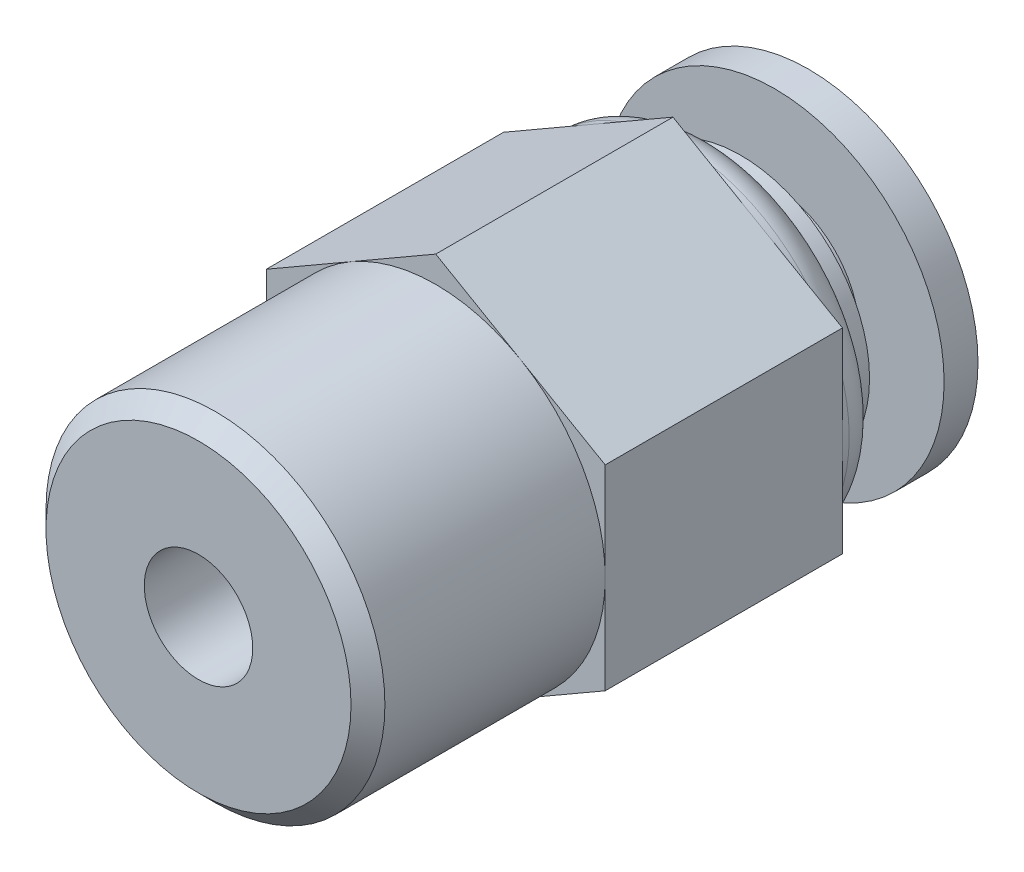
SolidWorks part; units mm, degrees
note: The reader was unsure of these and kept them because the rebuilt part matched: shared geometry of "Эскиз1<4>", "Эскиз1<5>", "Эскиз1<6>", "Эскиз1<8>", "Эскиз1<10>", "Эскиз1<11>".
material "Простая углеродистая сталь"
ref_plane "Спереди" through (0, 0, 0) normal (0, 0, 1) x (1, 0, 0)
ref_plane "Сверху" through (0, 0, 0) normal (0, 1, 0) x (1, 0, 0)
ref_plane "Справа" through (0, 0, 0) normal (1, 0, 0) x (0, 0, -1)
sketch "Эскиз1" plane through (0, 0, 0) normal (0, 0, 1) x (1, 0, 0)
  line L3 (0, 5.7735) -> (-5, 2.8868)
  line L4 (-5, 2.8868) -> (-5, -2.8868)
  line L5 (-5, -2.8868) -> (0, -5.7735)
  line L6 (0, -5.7735) -> (5, -2.8868)
  line L7 (5, -2.8868) -> (5, 2.8868)
  line L8 (5, 2.8868) -> (0, 5.7735)
  circle A0 centre (0, 0) radius 1.6
  circle A1 centre (0, 0) radius 3
  circle A2 centre (0, 0) radius 5 construction
  circle A3 centre (0, 0) radius 5
  circle A4 centre (0, 0) radius 4.3
  circle A5 centre (0, 0) radius 5
  circle A6 centre (0, 0) radius 3.8
  dimension "D1" = 3.2
  dimension "D2" = 6
  dimension "D3" = 10
  dimension "D4" = 8.6
  dimension "D5" = 10
  dimension "D6" = 10
extrude "Бобышка-Вытянуть2" add sketch "Эскиз1" along normal blind 7 contours L3 L4 L5 L6 L7 L8
extrude "Бобышка-Вытянуть3" add sketch "Эскиз1<4>" against normal blind 1.2 contours A3
sketch "Эскиз1<4>" plane through (0, 0, 0) normal (0, 0, 1) x (1, 0, 0) same geometry as "Эскиз1"
extrude "Бобышка-Вытянуть4" add sketch "Эскиз1<5>" along normal blind 14 contours A5
sketch "Эскиз1<5>" plane through (0, 0, 0) normal (0, 0, 1) x (1, 0, 0) same geometry as "Эскиз1"
cosmetic thread "Условное изображение резьбы1" parameters "D2"=4.891
extrude "Бобышка-Вытянуть5" add sketch "Эскиз1<6>" along normal blind 9 contours A4
sketch "Эскиз1<6>" plane through (0, 0, 0) normal (0, 0, 1) x (1, 0, 0) same geometry as "Эскиз1"
extrude "Бобышка-Вытянуть6" add sketch "Эскиз1<8>" against normal blind 2 contours A6
sketch "Эскиз1<8>" plane through (0, 0, 0) normal (0, 0, 1) x (1, 0, 0) same geometry as "Эскиз1"
fillet "Скругление1" radius 1 1 edges at (5, 0, -1.2)
extrude "Вырез-Вытянуть31" cut sketch "Эскиз1<10>" along normal through all from offset 2 contours A0 offset against normal yes
sketch "Эскиз1<10>" plane through (0, 0, 0) normal (0, 0, 1) x (1, 0, 0) same geometry as "Эскиз1"
extrude "Вырез-Вытянуть32" cut sketch "Эскиз1<11>" along normal blind 7 from offset 2 contours A1 offset against normal yes
sketch "Эскиз1<11>" plane through (0, 0, 0) normal (0, 0, 1) x (1, 0, 0) same geometry as "Эскиз1"
chamfer "Фаска1" distance 0.5 angle 45 1 edges at (5, 0, 14)
ref_plane "Плоскость1" through (0, 0, 0) normal (1, 0, 0) x (0, 0, -1)
sketch "Эскиз3" plane through (0, 0, 0) normal (1, 0, 0) x (0, 0, -1)
  line L0 (-1.3173, 0) -> (-26.6862, 0) construction
  line L1 (4, 2) -> (4, 5)
  line L2 (3, 5) -> (3, 2.5)
  line L3 (3, 2.5) -> (-5, 2.5)
  line L4 (-5, 2.5) -> (-5, 2)
  line L5 (-5, 0) -> (4, 0) construction
  line L6 (4, 2) -> (-5, 2)
  line L7 (4, 5) -> (3, 5)
  line L9 (-14, 4.5) -> (-14, -4.5) construction
  line L10 (4, 2) -> (4, 0) construction
  line L11 (-5, 2) -> (-5, 0) construction
  dimension "D1" = 10
  dimension "D2" = 5
  dimension "D3" = 1
  dimension "D4" = 8
  dimension "D5" = 4
  dimension "D6" = 4
  dimension "D7" = 18
surface "Поверхность-Повернуть1" sketch "Эскиз3" parameters "D1"=360
